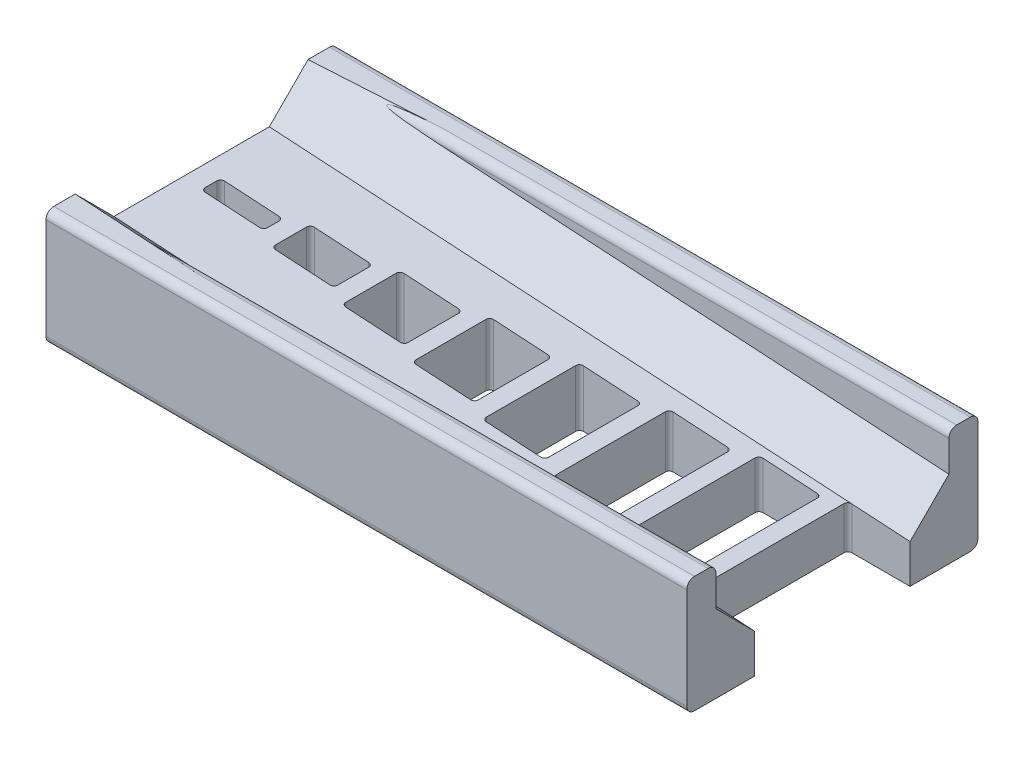
SolidWorks part; units mm, degrees
material "201 Annealed Stainless Steel (SS)"
ref_plane "Front Plane" through (0, 0, 0) normal (0, 0, 1) x (1, 0, 0)
ref_plane "Top Plane" through (0, 0, 0) normal (0, 1, 0) x (1, 0, 0)
ref_plane "Right Plane" through (0, 0, 0) normal (1, 0, 0) x (0, 0, -1)
sketch "Sketch1" plane through (0, 0, 0) normal (0, 0, 1) x (1, 0, 0)
  line L0 (-105.824, 0) -> (103.726, 0)
  line L1 (103.726, 0) -> (103.726, 12.7)
  line L2 (103.726, 12.7) -> (-105.824, 25.4)
  line L3 (-105.824, 25.4) -> (-105.824, 0)
  dimension "D1" = 209.55
  dimension "D2" = 12.7
  dimension "D3" = 25.4
  dimension "D4" = 103.726
extrude "Boss-Extrude1" add sketch "Sketch1" along normal mid plane 76.2
sketch "Sketch2" plane through (0, 0, -38.1) normal (0, 0, -1) x (-1, 0, 0)
  line L0 (-103.726, 0) -> (-103.726, 38.1)
  line L1 (-103.726, 38.1) -> (105.824, 38.1)
  line L2 (105.824, 38.1) -> (105.824, 0)
  line L3 (105.824, 0) -> (-103.726, 0)
  dimension "D1" = 38.1
extrude "Boss-Extrude2" add sketch "Sketch2" along normal blind 9.525 contours L1 L2 L3 L0
mirror "Mirror1" about plane through (0, 0, 0) normal (0, 0, 1) of "Boss-Extrude2"
sketch "Sketch3" plane through (0, 0, 0) normal (0, -1, 0) x (1, 0, 0)
  line L0 (-99.474, 3.175) -> (-99.474, -3.175)
  line L1 (-99.474, -3.175) -> (-79.154, -3.175)
  line L2 (-79.154, -3.175) -> (-79.154, 3.175)
  line L3 (-79.154, 3.175) -> (-99.474, 3.175)
  line L4 (103.726, 0) -> (-105.824, 0) construction
  line L5 (103.726, 47.625) -> (103.726, -47.625) construction
  line L6 (-52.992, 6.35) -> (-73.312, 6.35)
  line L7 (-73.312, 6.35) -> (-73.312, -6.35)
  line L8 (-73.312, -6.35) -> (-52.992, -6.35)
  line L9 (-52.992, -6.35) -> (-52.992, 6.35)
  line L10 (-26.83, 9.525) -> (-47.15, 9.525)
  line L11 (-47.15, 9.525) -> (-47.15, -9.525)
  line L12 (-47.15, -9.525) -> (-26.83, -9.525)
  line L13 (-26.83, -9.525) -> (-26.83, 9.525)
  line L14 (-0.668, 12.7) -> (-20.988, 12.7)
  line L15 (-20.988, 12.7) -> (-20.988, -12.7)
  line L16 (-20.988, -12.7) -> (-0.668, -12.7)
  line L17 (-0.668, -12.7) -> (-0.668, 12.7)
  line L18 (25.494, 15.875) -> (5.174, 15.875)
  line L19 (5.174, 15.875) -> (5.174, -15.875)
  line L20 (5.174, -15.875) -> (25.494, -15.875)
  line L21 (25.494, -15.875) -> (25.494, 15.875)
  line L22 (51.656, 19.05) -> (31.336, 19.05)
  line L23 (31.336, 19.05) -> (31.336, -19.05)
  line L24 (31.336, -19.05) -> (51.656, -19.05)
  line L25 (51.656, -19.05) -> (51.656, 19.05)
  line L26 (77.818, 22.225) -> (57.498, 22.225)
  line L27 (57.498, 22.225) -> (57.498, -22.225)
  line L28 (57.498, -22.225) -> (77.818, -22.225)
  line L29 (77.818, -22.225) -> (77.818, 22.225)
  line L30 (103.726, 25.4) -> (83.406, 25.4)
  line L31 (83.406, 25.4) -> (83.406, -25.4)
  line L32 (83.406, -25.4) -> (103.726, -25.4)
  line L33 (103.726, -25.4) -> (103.726, 25.4)
  line L34 (-105.824, 47.625) -> (-105.824, -47.625) construction
  point P2 (103.726, 0)
  point P7 (77.818, 0)
  point P9 (57.498, 0)
  point P38 (51.656, 0)
  point P39 (31.336, 0)
  point P40 (25.494, 0)
  point P44 (-79.154, 0)
  point P45 (-52.992, 0)
  point P46 (-26.83, 0)
  point P47 (-0.668, 0)
  dimension "D1" = 50.8
  dimension "D2" = 44.45
  dimension "D3" = 38.1
  dimension "D4" = 31.75
  dimension "D6" = 19.05
  dimension "D5" = 25.4
  dimension "D7" = 12.7
  dimension "D8" = 6.35
  dimension "D9" = 6.35
  dimension "D10" = 26.67
  dimension "D11" = 32.512
  dimension "D12" = 58.674
  dimension "D13" = 84.836
  dimension "D14" = 110.998
  dimension "D15" = 137.16
  dimension "D16" = 163.322
extrude "Cut-Extrude1" cut sketch "Sketch3" against normal through all
fillet "Fillet1" radius 1.27 30 edges at (77.818, 7.1351, -22.225) (51.656, 7.9279, -19.05) (25.494, 8.7207, -15.875) (-0.668, 9.5135, -12.7) (-26.83, 10.3062, -9.525) (-52.992, 11.099, -6.35) (-79.154, 11.8918, -3.175) (-79.154, 11.8918, 3.175) (-52.992, 11.099, 6.35) (-26.83, 10.3062, 9.525) (-0.668, 9.5135, 12.7) (25.494, 8.7207, 15.875) (51.656, 7.9279, 19.05) (77.818, 7.1351, 22.225) (83.406, 6.9658, -25.4) (57.498, 7.7508, -22.225) (31.336, 8.5436, -19.05) (5.174, 9.3364, -15.875) (-20.988, 10.1292, -12.7) (-47.15, 10.922, -9.525) (-73.312, 11.7148, -6.35) (-99.474, 12.5076, -3.175) (-99.474, 12.5076, 3.175) (-73.312, 11.7148, 6.35) (-47.15, 10.922, 9.525) (-20.988, 10.1292, 12.7) (5.174, 9.3364, 15.875) (31.336, 8.5436, 19.05) (57.498, 7.7508, 22.225) (83.406, 6.9658, 25.4)
chamfer "Chamfer1" distance 12.7 angle 45 2 edges at (-1.049, 19.05, 38.1) (-1.049, 19.05, -38.1)
fillet "Fillet2" radius 2.54 6 edges at (-1.049, 0, -47.625) (-1.049, 38.1, -47.625) (-0.8567, 38.1, -38.1) (-1.049, 0, 47.625) (-1.049, 38.1, 47.625) (-0.8567, 38.1, 38.1)
